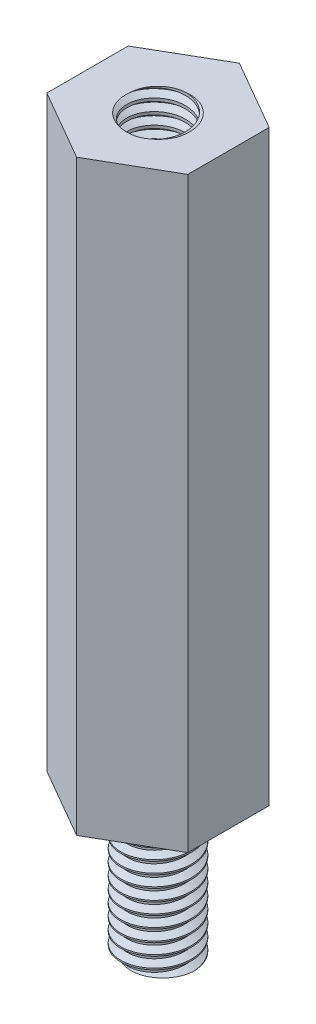
SolidWorks part; units mm, degrees
material "Brass"
ref_plane "Front Plane" through (0, 0, 0) normal (0, 0, 1) x (1, 0, 0)
ref_plane "Top Plane" through (0, 0, 0) normal (0, 1, 0) x (1, 0, 0)
ref_plane "Right Plane" through (0, 0, 0) normal (1, 0, 0) x (0, 0, -1)
sketch "Sketch1" plane through (0, 0, 0) normal (0, 1, 0) x (1, 0, 0)
  line L1 (3, 1.7321) -> (0, 3.4641)
  line L2 (0, 3.4641) -> (-3, 1.7321)
  line L3 (-3, 1.7321) -> (-3, -1.7321)
  line L4 (-3, -1.7321) -> (0, -3.4641)
  line L5 (0, -3.4641) -> (3, -1.7321)
  line L6 (3, -1.7321) -> (3, 1.7321)
  circle A0 centre (0, 0) radius 3 construction
  dimension "D1" = 6
extrude "Boss-Extrude1" add sketch "Sketch1" along normal blind 25 contours L2 L3 L4 L5 L6 L1
sketch "Sketch2" plane through (0, 0, 0) normal (0, -1, 0) x (1, 0, 0)
  circle A0 centre (0, 0) radius 1.5
  dimension "D1" = 3
extrude "Boss-Extrude2" add sketch "Sketch2" along normal blind 6
hole_wizard "Tap Drill for M3 Tap1" positions "Sketch3" profile "Sketch4" hole size "M3" standard "ISO"
sketch "Sketch3" plane through (0, 25, 0) normal (0, 1, 0) x (1, 0, 0)
  point P0 (0, 0)
sketch "Sketch4" plane through (0, 25, 0) normal (1, 0, 0) x (0, 0, 1)
  line L0 (0, 0) -> (0, 10.7511)
  line L1 (0, 10.7511) -> (1.25, 10)
  line L2 (1.25, 10) -> (1.25, 0)
  line L5 (1.25, 0) -> (0, 0)
  line L10 (0, 10.7511) -> (-1.25, 10) construction
  line L11 (0, -6.35) -> (0, 107.95) construction
  dimension "Hole Dia." = 2.5
  dimension "Hole Depth" = 10
  dimension "Drill Angle" = 118
thread "Thread1" pitch 0.5 method cut trim with start face yes profile "Thread Profile1" start angle 0, offset 1, length 9, pitch 0.5, diameter 2.5
ref_plane "Plane1" through (-1.25, 26, 0) normal (0, 0, 1) x (-1, 0, 0)
sketch "Thread Profile1" plane through (-1.25, 26, 0) normal (0, 0, 1) x (-1, 0, 0)
  line L0 (0, 0) -> (0, 0.5) construction
  line L1 (0, 0) -> (0.2706, 0.1562)
  line L2 (0.2706, 0.1562) -> (0.2706, 0.2187)
  line L3 (0.2706, 0.2187) -> (0, 0.375)
  line L4 (0.2706, 0.1875) -> (0, 0.1875) construction
  line L11 (0, 0) -> (0, 0.375)
  point P2 (0, 0)
  dimension "Pitch" = 0.5
  dimension "Profile_Angle" = 60
  dimension "Profile_Land" = 0.0625
  dimension "Profile_Height" = 0.2706
thread "Thread2" pitch 0.5 method cut profile "Thread Profile2" start angle 0, offset 1, length 6.5, pitch 0.5, diameter 3
ref_plane "Plane2" through (1.5, -7, 0) normal (0, 0, 1) x (1, 0, 0)
sketch "Thread Profile2" plane through (1.5, -7, 0) normal (0, 0, 1) x (1, 0, 0)
  line L0 (0, 0) -> (0, 0.5) construction
  line L11 (0, 0) -> (0, 0.4375)
  line L12 (0, 0.4375) -> (-0.2706, 0.2812)
  line L13 (-0.2706, 0.2812) -> (-0.2706, 0.1562)
  line L15 (-0.2706, 0.1562) -> (0, 0)
  line L17 (-0.2706, 0.2187) -> (0, 0.2187) construction
  point P2 (0, 0)
  dimension "Pitch" = 0.5
  dimension "Profile_Angle" = 60
  dimension "Profile_Land" = 0.125
  dimension "Profile_Height" = 0.2706
sketch "Sketch9" plane through (0, 0, 0) normal (0, 1, 0) x (1, 0, 0)
  circle A0 centre (0, 0) radius 1.225
  dimension "D1" = 2.45
extrude "Cut-Extrude-Thin1" cut sketch "Sketch9" against normal blind 0.5 thin contours A0 thin type one direction wall 10
